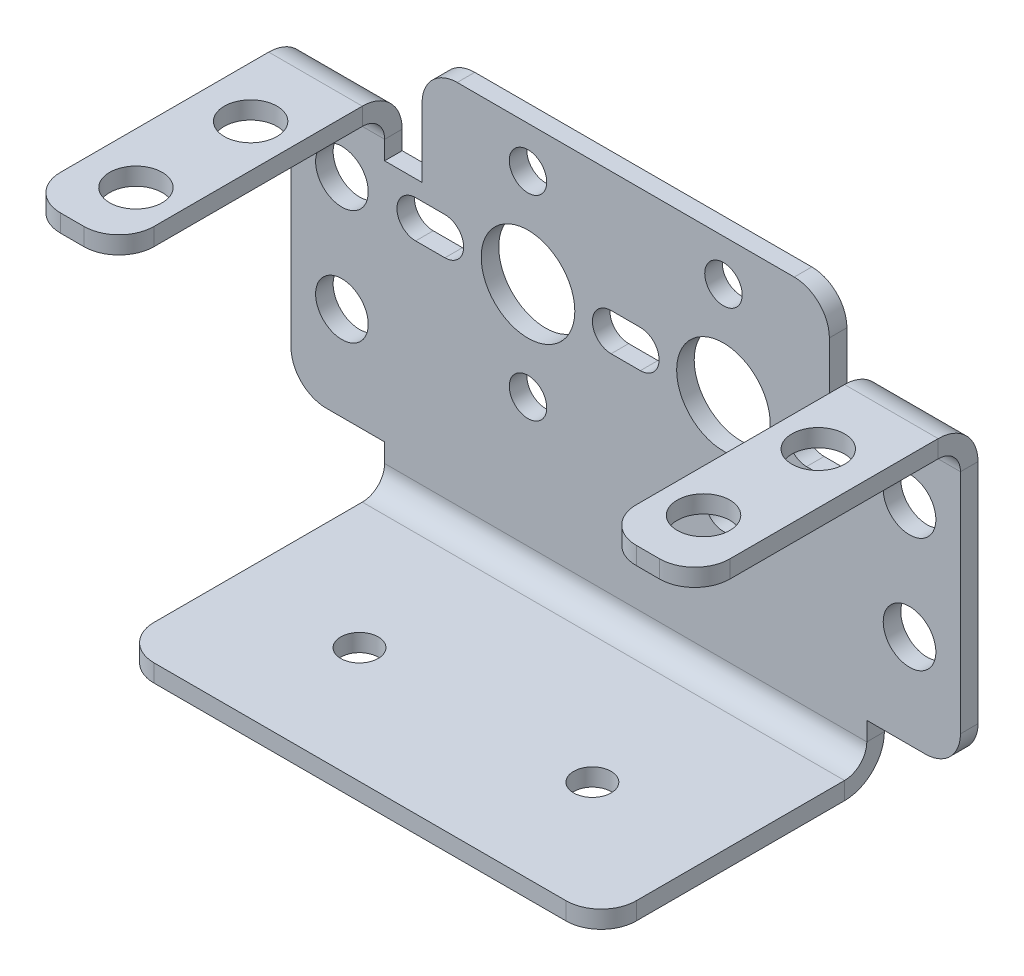
SolidWorks part; units mm, degrees
note: The reader was unsure of these and kept them because the rebuilt part matched: flange length of "Tôle pliée sur arête1", "Tôle pliée sur arête2", "Tôle pliée sur arête3".
ref_plane "Plan de face" through (0, 0, 0) normal (0, 0, 1) x (1, 0, 0)
ref_plane "Plan de dessus" through (0, 0, 0) normal (0, 1, 0) x (1, 0, 0)
ref_plane "Plan de droite" through (0, 0, 0) normal (1, 0, 0) x (0, 0, -1)
sketch "Esquisse1" plane through (0, 0, 0) normal (0, 0, 1) x (1, 0, 0)
  line L0 (51.02, 185.0049) -> (108.22, 185.0049) construction
  line L1 (52.8602, 174.0393) -> (110.0602, 174.0393) construction
  line L2 (52.6848, 187.6956) -> (52.6848, 166.1151)
  line L3 (55.6848, 163.1151) -> (60.6848, 163.1151)
  line L4 (60.6848, 163.1151) -> (60.6848, 158.1151)
  line L5 (60.6848, 158.1151) -> (101.8848, 158.1151)
  line L6 (63.3348, 180.9151) -> (65.8348, 180.9151) construction
  line L7 (63.3348, 182.5151) -> (65.8348, 182.5151)
  line L8 (63.3348, 179.3151) -> (65.8348, 179.3151)
  line L9 (72.9348, 180.9151) -> (72.9348, 189.2651) construction
  line L10 (82.5348, 180.9151) -> (80.0348, 180.9151) construction
  line L11 (82.5348, 182.5151) -> (80.0348, 182.5151)
  line L12 (82.5348, 179.3151) -> (80.0348, 179.3151)
  line L13 (95.6848, 192.8151) -> (66.8848, 192.8151)
  line L14 (63.8848, 189.8151) -> (63.8848, 183.9151)
  line L15 (63.8848, 183.9151) -> (60.6848, 183.9151)
  line L16 (60.6848, 183.9151) -> (60.6848, 188.9151)
  line L17 (60.6848, 188.9151) -> (52.6848, 188.9151)
  line L18 (52.6848, 188.9151) -> (52.6848, 187.6956)
  line L19 (81.2848, 192.8151) -> (81.2848, 158.1151) construction
  line L20 (89.6348, 180.9151) -> (89.6348, 189.2651) construction
  line L21 (109.8848, 188.9151) -> (109.8848, 187.6956)
  line L22 (101.8848, 188.9151) -> (109.8848, 188.9151)
  line L23 (101.8848, 183.9151) -> (101.8848, 188.9151)
  line L24 (98.6848, 183.9151) -> (101.8848, 183.9151)
  line L25 (98.6848, 189.8151) -> (98.6848, 183.9151)
  line L26 (101.8848, 163.1151) -> (101.8848, 158.1151)
  line L27 (106.8848, 163.1151) -> (101.8848, 163.1151)
  line L28 (109.8848, 187.6956) -> (109.8848, 166.1151)
  line L29 (99.2348, 180.9151) -> (96.7348, 180.9151) construction
  line L30 (99.2348, 182.5151) -> (96.7348, 182.5151)
  line L31 (99.2348, 179.3151) -> (96.7348, 179.3151)
  arc A0 (52.6848, 166.1151) -> (55.6848, 163.1151) centre (55.6848, 166.1151) ccw
  circle A1 centre (57.0348, 180.9151) radius 2.25
  circle A2 centre (57.0348, 171.1151) radius 2.25
  arc A3 (66.8848, 192.8151) -> (63.8848, 189.8151) centre (66.8848, 189.8151) ccw
  circle A4 centre (72.9348, 180.9151) radius 4
  circle A5 centre (72.9348, 189.2651) radius 1.6
  circle A6 centre (72.9348, 172.5651) radius 1.6
  arc A7 (63.3348, 182.5151) -> (63.3348, 179.3151) centre (63.3348, 180.9151) ccw
  arc A8 (65.8348, 179.3151) -> (65.8348, 182.5151) centre (65.8348, 180.9151) ccw
  arc A9 (82.5348, 179.3151) -> (82.5348, 182.5151) centre (82.5348, 180.9151) ccw
  arc A10 (80.0348, 179.3151) -> (80.0348, 182.5151) centre (80.0348, 180.9151) cw
  circle A11 centre (89.6348, 172.5651) radius 1.6
  circle A12 centre (89.6348, 189.2651) radius 1.6
  circle A13 centre (89.6348, 180.9151) radius 4
  arc A14 (95.6848, 192.8151) -> (98.6848, 189.8151) centre (95.6848, 189.8151) cw
  circle A15 centre (105.5348, 171.1151) radius 2.25
  circle A16 centre (105.5348, 180.9151) radius 2.25
  arc A17 (109.8848, 166.1151) -> (106.8848, 163.1151) centre (106.8848, 166.1151) cw
  arc A18 (99.2348, 182.5151) -> (99.2348, 179.3151) centre (99.2348, 180.9151) cw
  arc A19 (96.7348, 179.3151) -> (96.7348, 182.5151) centre (96.7348, 180.9151) cw
  point P20 (64.5848, 180.9151)
  point P36 (81.2848, 182.5151)
  point P38 (81.2848, 180.9151)
  point P44 (81.2848, 180.9151)
  point P67 (81.2848, 179.3151)
  point P71 (97.9848, 180.9151)
  dimension "D5" = 8.9
  dimension "D6" = 3
  dimension "D11" = 4.5
  dimension "D12" = 4.5
  dimension "D15" = 8
  dimension "D18" = 3.2
  dimension "D19" = 3.2
  dimension "D22" = 1.6
  dimension "D23" = 3
  dimension "D1" = 57.2
  dimension "D2" = 57.2
  dimension "D3" = 5
  dimension "D4" = 28.6
  dimension "D7" = 5
  dimension "D8" = 8
  dimension "D9" = 3.2
  dimension "D10" = 34.7
  dimension "D13" = 13
  dimension "D14" = 9.8
  dimension "D16" = 8.35
  dimension "D17" = 16.7
  dimension "D20" = 8.35
  dimension "D21" = 2.5
  dimension "D24" = 16.7
  dimension "D25" = 11.9
  dimension "D26" = 24.25
  dimension "D27" = 20.6
base flange "Tôle de base pliée1" sketch "Esquisse1" thickness 1.5 reverse thickness direction no parameters "D1"=1.905
edge flange "Tôle pliée sur arête1" sketch "Esquisse8" flange angle 90 flange length 24.2 bend radius 1.905 thickness 1.5 relief rectangular parameters "D6"=10
sketch "Esquisse8" plane through (0, 158.1151, 0) normal (0, -1, 0) x (1, 0, 0)
  line L2 (60.6848, 0) -> (60.6848, 22.7)
  line L3 (60.6848, 22.7) -> (101.8848, 22.7)
  line L4 (101.8848, 22.7) -> (101.8848, 0)
  line L7 (60.6848, 0) -> (101.8848, 0) construction
  line L8 (60.6848, 0) -> (101.8848, 0)
bend "Pli d'arête1" bend radius 1.905 bend angle 90 parameters "D5"=1
fillet "Congé1" radius 3 2 edges at (60.6848, 158.8651, 22.7) (101.8848, 158.8651, 22.7)
sketch "Esquisse9" plane through (0, 159.6151, 0) normal (0, 1, 0) x (1, 0, 0)
  line L0 (95.6848, 1.5) -> (66.8848, 1.5) construction
  line L1 (60.6848, -19.7) -> (60.6848, -1.905) construction
  circle A0 centre (71.3348, -12.8) radius 1.6
  circle A1 centre (91.2348, -12.8) radius 1.6
  dimension "D1" = 3.2
  dimension "D2" = 3.2
  dimension "D3" = 19.9
  dimension "D4" = 14.3
  dimension "D5" = 10.65
extrude "Enlèv. mat.-Extru.1" cut sketch "Esquisse9" against normal blind 10 normal cut yes
edge flange "Tôle pliée sur arête2" sketch "Esquisse12" flange angle 90 flange length 24.2 bend radius 1.905 thickness 1.5 relief rectangular parameters "D6"=10
sketch "Esquisse12" plane through (0, 188.9151, 0) normal (0, 1, 0) x (-1, 0, 0)
  line L2 (-60.6848, 0) -> (-60.6848, 22.7)
  line L3 (-60.6848, 22.7) -> (-52.6848, 22.7)
  line L4 (-52.6848, 22.7) -> (-52.6848, 0)
  line L5 (-60.6848, 0) -> (-52.6848, 0) construction
  line L6 (-60.6848, 0) -> (-52.6848, 0)
bend "Pli d'arête2" bend radius 1.905 bend angle 90 parameters "D5"=2
edge flange "Tôle pliée sur arête3" sketch "Esquisse15" flange angle 90 flange length 24.2 bend radius 1.905 thickness 1.5 relief rectangular parameters "D6"=10
sketch "Esquisse15" plane through (0, 188.9151, 0) normal (0, 1, 0) x (-1, 0, 0)
  line L2 (-109.8848, 0) -> (-109.8848, 22.7)
  line L3 (-109.8848, 22.7) -> (-101.8848, 22.7)
  line L4 (-101.8848, 22.7) -> (-101.8848, 0)
  line L5 (-109.8848, 0) -> (-101.8848, 0) construction
  line L6 (-109.8848, 0) -> (-101.8848, 0)
bend "Pli d'arête3" bend radius 1.905 bend angle 90 parameters "D5"=3
fillet "Congé2" radius 3 4 edges at (109.8848, 188.1651, 22.7) (101.8848, 188.1651, 22.7) (52.6848, 188.1651, 22.7) (60.6848, 188.1651, 22.7)
sketch "Esquisse16" plane through (0, 188.9151, 0) normal (0, 1, 0) x (1, 0, 0)
  line L0 (52.6848, 1.5) -> (60.6848, 1.5) construction
  line L2 (95.6848, 1.5) -> (66.8848, 1.5) construction
  circle A0 centre (57.0348, -7.8) radius 2.25
  circle A1 centre (57.0348, -17.6) radius 2.25
  circle A2 centre (105.5348, -7.8) radius 2.25
  circle A3 centre (105.5348, -17.6) radius 2.25
  point P14 (81.2848, 1.5)
  dimension "D1" = 4.5
  dimension "D2" = 4.5
  dimension "D3" = 9.3
  dimension "D4" = 9.8
  dimension "D5" = 24.25
  dimension "D6" = 48.5
extrude "Enlèv. mat.-Extru.2" cut sketch "Esquisse16" against normal blind 10 normal cut yes
sketch "Lignes de pliage1" [suppressed] plane through (0, 0, 0) normal (0, 1, 0) x (1, 0, 0)
sketch "Cube de visualisation1" [suppressed] plane through (0, 0, 0) normal (0, 1, 0) x (1, 0, 0)
sheet metal parameters "Tôlerie1" thickness 1.5 parameters "D1"=1.905
flat pattern "Etat déplié1" [suppressed]
sketch "Lignes de pliage2" plane through (0, 0, 0) normal (0, 1, 0) x (1, 0, 0)
sketch3d "Cube de visualisation2" [suppressed]
  line L0 (3, 26.7, 0) -> (-54.2, 26.7, 0) construction
  line L1 (3, -8, 0) -> (-54.2, -8, 0) construction
  line L2 (3, 26.7, 0) -> (3, -8, 0) construction
  line L3 (-54.2, 26.7, 0) -> (-54.2, -8, 0) construction
sheet metal parameters "Tôlerie2" thickness 1.5 parameters "D1"=1.905
flat pattern "Etat déplié1"
sketch "Lignes de pliage2" plane through (0, 0, 0) normal (0, 0, 1) x (1, 0, 0)
  line L0 (60.6848, 159.4349) -> (101.8848, 159.4349) construction
  line L1 (60.6848, 159.4349) -> (101.8848, 159.4349) construction
sketch3d "Cube de visualisation2" [suppressed]
  line L0 (-3, 26.7, 0) -> (54.2, 26.7, 0) construction
  line L1 (-3, -29.5605, 0) -> (54.2, -29.5605, 0) construction
  line L2 (-3, 26.7, 0) -> (-3, -29.5605, 0) construction
  line L3 (54.2, 26.7, 0) -> (54.2, -29.5605, 0) construction
bend of the flat pattern "Dépliage-<Pli d'arête1>1"
sheet metal parameters "Tôlerie3" thickness 1.5 parameters "D1"=1.905
flat pattern "Etat déplié1"
sketch "Lignes de pliage2" plane through (0, 0, 0) normal (0, 0, 1) x (1, 0, 0)
  line L0 (60.6848, 159.4349) -> (101.8848, 159.4349) construction
  line L1 (60.6848, 159.4349) -> (101.8848, 159.4349) construction
sketch3d "Cube de visualisation2" [suppressed]
  line L0 (-3, 26.7, 0) -> (54.2, 26.7, 0) construction
  line L1 (-3, -29.5605, 0) -> (54.2, -29.5605, 0) construction
  line L2 (-3, 26.7, 0) -> (-3, -29.5605, 0) construction
  line L3 (54.2, 26.7, 0) -> (54.2, -29.5605, 0) construction
bend of the flat pattern "Dépliage-<Pli d'arête1>1"
sheet metal parameters "Tôlerie4" thickness 1.5 parameters "D1"=1.905
flat pattern "Etat déplié1"
sketch "Lignes de pliage2" plane through (0, 0, 0) normal (0, 0, 1) x (1, 0, 0)
  line L0 (60.6848, 159.4349) -> (101.8848, 159.4349) construction
  line L1 (60.6848, 159.4349) -> (101.8848, 159.4349) construction
  line L2 (60.6848, 187.5953) -> (52.6848, 187.5953) construction
  line L3 (60.6848, 187.5953) -> (52.6848, 187.5953) construction
sketch3d "Cube de visualisation2" [suppressed]
  line L0 (54.2, -29.5605, 0) -> (54.2, 44.3605, 0) construction
  line L1 (-3, -29.5605, 0) -> (-3, 44.3605, 0) construction
  line L2 (54.2, -29.5605, 0) -> (-3, -29.5605, 0) construction
  line L3 (54.2, 44.3605, 0) -> (-3, 44.3605, 0) construction
bend of the flat pattern "Dépliage-<Pli d'arête1>1"
bend of the flat pattern "Dépliage-<Pli d'arête2>1"
sheet metal parameters "Tôlerie5" thickness 1.5 parameters "D1"=1.905
flat pattern "Etat déplié1"
sketch "Lignes de pliage2" plane through (0, 0, 0) normal (0, 0, 1) x (1, 0, 0)
  line L0 (60.6848, 159.4349) -> (101.8848, 159.4349) construction
  line L1 (60.6848, 159.4349) -> (101.8848, 159.4349) construction
  line L2 (60.6848, 187.5953) -> (52.6848, 187.5953) construction
  line L3 (60.6848, 187.5953) -> (52.6848, 187.5953) construction
  line L4 (109.8848, 187.5953) -> (101.8848, 187.5953) construction
  line L5 (109.8848, 187.5953) -> (101.8848, 187.5953) construction
sketch3d "Cube de visualisation2" [suppressed]
  line L0 (54.2, -29.5605, 0) -> (54.2, 44.3605, 0) construction
  line L1 (-3, -29.5605, 0) -> (-3, 44.3605, 0) construction
  line L2 (54.2, -29.5605, 0) -> (-3, -29.5605, 0) construction
  line L3 (54.2, 44.3605, 0) -> (-3, 44.3605, 0) construction
bend of the flat pattern "Dépliage-<Pli d'arête1>1"
bend of the flat pattern "Dépliage-<Pli d'arête2>1"
bend of the flat pattern "Dépliage-<Pli d'arête3>1"
sheet metal parameters "Tôlerie6" thickness 1.5 parameters "D1"=1.905
flat pattern "Etat déplié1"
sketch "Lignes de pliage2" plane through (0, 0, 0) normal (0, 0, 1) x (1, 0, 0)
  line L0 (60.6848, 159.4349) -> (101.8848, 159.4349) construction
  line L1 (60.6848, 159.4349) -> (101.8848, 159.4349) construction
  line L2 (60.6848, 187.5953) -> (52.6848, 187.5953) construction
  line L3 (60.6848, 187.5953) -> (52.6848, 187.5953) construction
  line L4 (109.8848, 187.5953) -> (101.8848, 187.5953) construction
  line L5 (109.8848, 187.5953) -> (101.8848, 187.5953) construction
sketch3d "Cube de visualisation2" [suppressed]
  line L0 (54.2, -29.5605, 0) -> (54.2, 44.3605, 0) construction
  line L1 (-3, -29.5605, 0) -> (-3, 44.3605, 0) construction
  line L2 (54.2, -29.5605, 0) -> (-3, -29.5605, 0) construction
  line L3 (54.2, 44.3605, 0) -> (-3, 44.3605, 0) construction
bend of the flat pattern "Dépliage-<Pli d'arête1>1"
bend of the flat pattern "Dépliage-<Pli d'arête2>1"
bend of the flat pattern "Dépliage-<Pli d'arête3>1"
